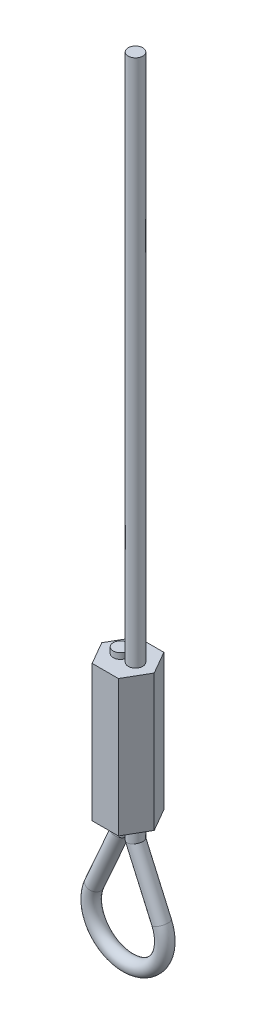
SolidWorks part; units mm, degrees
ref_plane "Plano frontal" through (0, 0, 0) normal (0, 0, 1) x (1, 0, 0)
ref_plane "Plano superior" through (0, 0, 0) normal (0, 1, 0) x (1, 0, 0)
ref_plane "Plano direito" through (0, 0, 0) normal (1, 0, 0) x (0, 0, -1)
sketch "Esboço1" plane through (0, 0, 0) normal (0, 0, 1) x (1, 0, 0)
  line L0 (0, 0) -> (0, 20) construction
  line L1 (1.65, 16.275) -> (7.406, 3.2805)
  line L2 (-1.65, 16.275) -> (-7.406, 3.2805)
  line L3 (1.65, 166.275) -> (1.65, 16.275)
  line L4 (-1.65, 51.275) -> (-1.65, 16.275)
  arc A0 (-7.406, 3.2805) -> (7.406, 3.2805) centre (0, 0) ccw
  dimension "D1" = 16.2
  dimension "D2" = 20
  dimension "D3" = 1.65
  dimension "D4" = 1.65
  dimension "D5" = 35
  dimension "D6" = 150
  dimension "D7" = 3.3
ref_plane "Plano1" through (1.65, 166.275, 0) normal (0, -1, 0) x (1, 0, 0)
sketch "Esboço2" plane through (1.65, 166.275, 0) normal (0, -1, 0) x (1, 0, 0)
  circle A0 centre (0, 0) radius 1.6
  dimension "D1" = 3.2
sweep "Varredura1" add profiles "Esboço2" path "Esboço1"
sketch "Esboço3" plane through (0, 0, 0) normal (0, 1, 0) x (1, 0, 0)
  line L0 (0, 0) -> (0, -9.9383) construction
ref_axis "Eixo1" through (0, 0, 9.9383) along (0, 0, -1)
ref_plane "Plano2" through (0, 20, 0) normal (0, 1, 0) x (-1, 0, 0)
sketch "Esboço4" plane through (0, 20, 0) normal (0, 1, 0) x (-1, 0, 0)
  line L1 (-5.7735, 0) -> (-2.8868, -5)
  line L2 (-2.8868, -5) -> (2.8868, -5)
  line L3 (2.8868, -5) -> (5.7735, 0)
  line L4 (5.7735, 0) -> (2.8868, 5)
  line L5 (2.8868, 5) -> (-2.8868, 5)
  line L6 (-2.8868, 5) -> (-5.7735, 0)
  circle A0 centre (0, 0) radius 5 construction
  dimension "D1" = 10
extrude "Extrusão1" add sketch "Esboço4" along normal blind 30
